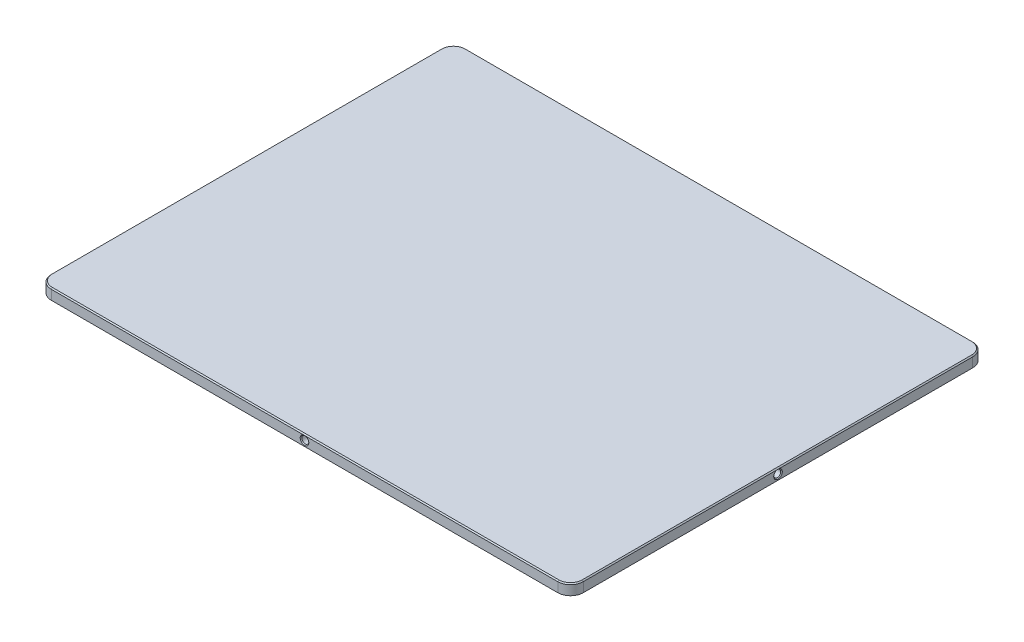
SolidWorks part; units mm, degrees
material "Простая углеродистая сталь"
ref_plane "Front" through (0, 0, 0) normal (0, 0, 1) x (1, 0, 0)
ref_plane "Top" through (0, 0, 0) normal (0, 1, 0) x (1, 0, 0)
ref_plane "Right" through (0, 0, 0) normal (1, 0, 0) x (0, 0, -1)
sketch "Эскиз1" plane through (0, 0, 0) normal (0, 1, 0) x (1, 0, 0)
  line L1 (-125, 97.5) -> (125, 97.5)
  line L2 (-125, 97.5) -> (-125, -97.5)
  line L3 (-125, -97.5) -> (125, -97.5)
  line L4 (125, 97.5) -> (125, -97.5)
  point P0 (0, 0)
  point P6 (0, 97.5)
  point P7 (0, -97.5)
  point P8 (-125, 0)
  dimension "D1" = 250
  dimension "D3" = 195
extrude "База" add sketch "Эскиз1" along normal blind 5
hole_wizard "Резьба-1-M4" positions "Эскиз4" profile "Эскиз5" tap size "M4" standard "DIN"
sketch "Эскиз4" plane through (125, 0, 0) normal (1, 0, 0) x (0, 0, -1)
  line L1 (-97.5, 5) -> (-97.5, 0) construction
  point P0 (0, 2.5)
  point P42 (-97.5, 2.5)
sketch "Эскиз5" plane through (125, 2.5, 0) normal (0, 1, 0) x (0, 0, -1)
  line L0 (0, 0) -> (0, 40.9914)
  line L1 (0, 40.9914) -> (1.65, 40)
  line L2 (1.65, 40) -> (1.65, 0.375)
  line L3 (1.65, 0.375) -> (2.025, 0)
  line L5 (2.025, 0) -> (0, 0)
  line L6 (-1.65, 0.375) -> (-2.025, 0) construction
  line L10 (0, 40.9914) -> (-1.65, 40) construction
  line L11 (0, -6.35) -> (0, 107.95) construction
  dimension "Диаметр сверла" = 3.3
  dimension "Глубина сверла" = 40
  dimension "Диаметр передней зенковки" = 4.05
  dimension "Угол передней зенковки" = 90
  dimension "Угол заточки сверла" = 118
cosmetic thread "Отверстие резьбы3"
hole_wizard "Резьба-2-M4" positions "Эскиз8" profile "Эскиз9" tap size "M4" standard "DIN"
sketch "Эскиз8" plane through (-125, 0, 0) normal (-1, 0, 0) x (0, 0, 1)
  point P0 (0, 2.5)
sketch "Эскиз9" plane through (-125, 2.5, 0) normal (0, 1, 0) x (0, 0, 1)
  line L0 (0, 0) -> (0, 40.9914)
  line L1 (0, 40.9914) -> (1.65, 40)
  line L2 (1.65, 40) -> (1.65, 0.375)
  line L3 (1.65, 0.375) -> (2.025, 0)
  line L5 (2.025, 0) -> (0, 0)
  line L6 (-1.65, 0.375) -> (-2.025, 0) construction
  line L10 (0, 40.9914) -> (-1.65, 40) construction
  line L11 (0, -6.35) -> (0, 107.95) construction
  dimension "Диаметр сверла" = 3.3
  dimension "Глубина сверла" = 40
  dimension "Диаметр передней зенковки" = 4.05
  dimension "Угол передней зенковки" = 90
  dimension "Угол заточки сверла" = 118
cosmetic thread "Отверстие резьбы5"
hole_wizard "Резьба-3-M4" positions "Эскиз10" profile "Эскиз11" tap size "M4" standard "DIN"
sketch "Эскиз10" plane through (0, 0, 97.5) normal (0, 0, 1) x (1, 0, 0)
  line L0 (0, 0) -> (0, 2.5) construction
  line L1 (0, 2.5) -> (0, 5) construction
  line L2 (-125, 5) -> (125, 5) construction
  point P0 (0, 2.5)
sketch "Эскиз11" plane through (0, 2.5, 97.5) normal (1, 0, 0) x (0, -1, 0)
  line L0 (0, 0) -> (0, 40.9914)
  line L1 (0, 40.9914) -> (1.65, 40)
  line L2 (1.65, 40) -> (1.65, 0.375)
  line L3 (1.65, 0.375) -> (2.025, 0)
  line L5 (2.025, 0) -> (0, 0)
  line L6 (-1.65, 0.375) -> (-2.025, 0) construction
  line L10 (0, 40.9914) -> (-1.65, 40) construction
  line L11 (0, -6.35) -> (0, 107.95) construction
  dimension "Диаметр сверла" = 3.3
  dimension "Глубина сверла" = 40
  dimension "Диаметр передней зенковки" = 4.05
  dimension "Угол передней зенковки" = 90
  dimension "Угол заточки сверла" = 118
cosmetic thread "Отверстие резьбы6" parameters "D1"=35, "D2"=4
fillet "Скругление1" radius 6 4 edges at (125, 2.5, 97.5) (-125, 2.5, 97.5) (125, 2.5, -97.5) (-125, 2.5, -97.5)
chamfer "Фаска1" distance 0.5 angle 45 8 edges at (123.2426, 5, 95.7426) (123.2426, 5, -95.7426) (0, 5, -97.5) (-123.2426, 5, -95.7426) (-123.2426, 5, 95.7426) (0, 5, 97.5) (125, 5, 0) (-125, 5, 0)
